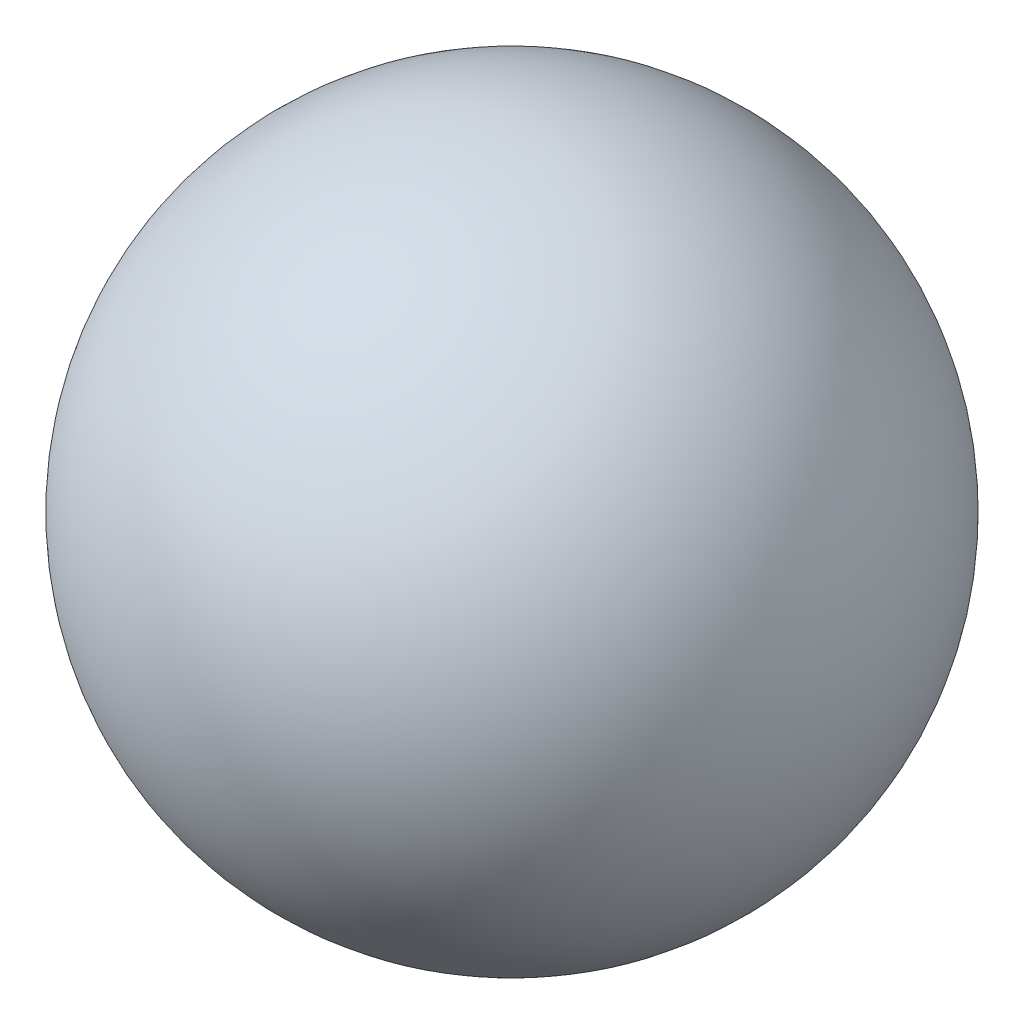
SolidWorks part; units mm, degrees
ref_plane "Front Plane" through (0, 0, 0) normal (0, 0, 1) x (1, 0, 0)
ref_plane "Top Plane" through (0, 0, 0) normal (0, 1, 0) x (1, 0, 0)
ref_plane "Right Plane" through (0, 0, 0) normal (1, 0, 0) x (0, 0, -1)
sketch "Sketch1" plane through (0, 0, 0) normal (0, 0, 1) x (1, 0, 0)
  line L0 (0, 0) -> (0, 1600)
  line L1 (0, 0) -> (0, -1600)
  circle A1 centre (0, 0) radius 1600
revolve "Revolve2" add sketch "Sketch1" angle 360 about L0 region at (679.0611, 0, 0)
